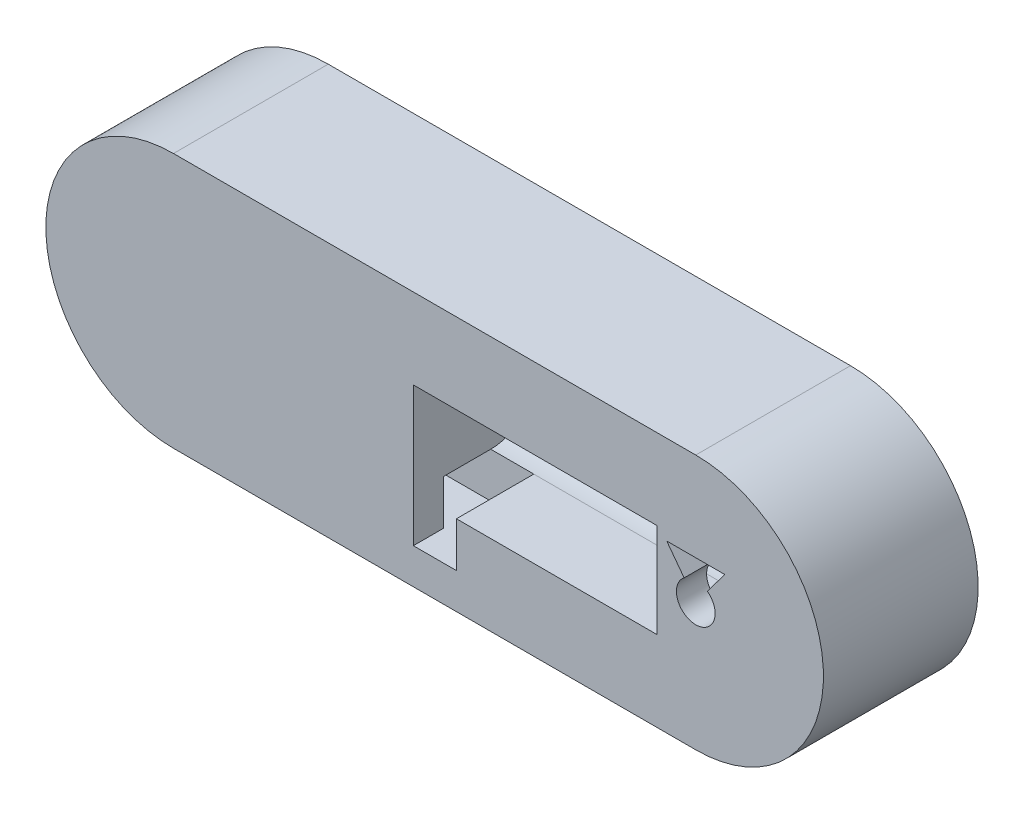
SolidWorks part; units mm, degrees
note: The reader was unsure of these and kept them because the rebuilt part matched: shared geometry of "Croquis1<4>".
ref_plane "Alzado" through (0, 0, 0) normal (0, 0, 1) x (1, 0, 0)
ref_plane "Planta" through (0, 0, 0) normal (0, 1, 0) x (1, 0, 0)
ref_plane "Vista lateral" through (0, 0, 0) normal (1, 0, 0) x (0, 0, -1)
sketch "Croquis1" plane through (0, 0, 0) normal (0, 0, 1) x (1, 0, 0)
  line L0 (-58.0271, -33) -> (76.9729, -33)
  line L1 (-58.0271, 33) -> (76.9729, 33)
  line L2 (-54.2341, 3.2577) -> (-54.2341, -3.2577)
  line L3 (69.4729, 10) -> (73.9729, 4)
  line L4 (73.9729, 4) -> (79.9729, 4)
  line L5 (79.9729, 4) -> (84.4729, 10)
  line L6 (84.4729, 10) -> (69.4729, 10)
  circle A0 centre (-58.0271, 0) radius 33
  circle A1 centre (76.9729, 0) radius 33
  circle A2 centre (-58.0271, 0) radius 5
  circle A3 centre (76.9729, 0) radius 5
  dimension "D2" = 10
  dimension "D3" = 10
  dimension "D4" = 66
  dimension "D1" = 135
  dimension "D5" = 15
  dimension "D6" = 6
extrude "Saliente-Extruir1" add sketch "Croquis1" along normal blind 40 contours A0 L0 A2 | A1 L1 A0 L0 | L1 A1 A3 | A2 | L2 A2
extrude "Cortar-Extruir2" cut sketch "Croquis1<4>" along normal blind 10 contours L2 A2
sketch "Croquis1<4>" plane through (0, 0, 0) normal (0, 0, 1) x (1, 0, 0) same geometry as "Croquis1"
sketch "Croquis5" plane through (0, 0, 40) normal (0, 0, 1) x (1, 0, 0)
  line L0 (15.1104, -23.8) -> (15.1104, -12.2)
  line L1 (15.1104, -12.2) -> (66.9729, -12.2)
  line L9 (3.9729, 12.2) -> (3.9729, -23.8)
  line L10 (66.9729, -12.2) -> (66.9729, 12.2)
  line L13 (3.9729, -23.8) -> (15.1104, -23.8)
  line L14 (66.9729, 12.2) -> (3.9729, 12.2)
  arc A0 (76.9729, -33) -> (76.9729, 33) centre (76.9729, 0) ccw construction
  arc A1 (76.9729, -33) -> (76.9729, 33) centre (76.9729, 0) ccw
  circle A2 centre (76.9729, 0) radius 5 construction
  circle A3 centre (76.9729, 0) radius 5
  point P2 (66.9729, 0)
  dimension "D2" = 10
  dimension "D3" = 63
  dimension "D4" = 24.4
  dimension "D1" = 11.6
extrude "Cortar-Extruir4" cut sketch "Croquis5" against normal blind 20 contours L10 L14 L9 L13 L0 L1
ref_plane "Plano2" through (3.9729, 0, 0) normal (1, 0, 0) x (0, 0, -1)
sketch "Croquis6" plane through (3.9729, 0, 0) normal (1, 0, 0) x (0, 0, -1)
  line L0 (-20, 12.2) -> (-40, 12.2)
  line L1 (-20, -12.2) -> (-40, -12.2)
  line L2 (-20, -23.8) -> (-20, -12.2)
  line L4 (-40, 12.2) -> (-40, -23.8)
  line L5 (-40, -23.8) -> (-20, -23.8)
  line L6 (-20, -23.8) -> (-20, 12.2)
  line L7 (-20, 12.2) -> (-40, 12.2)
  line L8 (-40, 12.2) -> (-40, -23.8)
  line L9 (-40, -23.8) -> (-20, -23.8)
  line L11 (-20, 12.2) -> (-40, 12.2)
  line L16 (0, -33) -> (0, 33)
  line L17 (0, 33) -> (-40, 33)
  line L18 (-40, 33) -> (-40, -33)
  line L19 (-40, -33) -> (0, -33)
  line L20 (0, -33) -> (0, 33)
  line L21 (0, 33) -> (-40, 33)
  line L22 (-40, 33) -> (-40, -33)
  line L23 (-40, -33) -> (0, -33)
  circle A0 centre (-20, 0) radius 12.2
  dimension "D2" = 24.4
  dimension "D3" = 0
  dimension "D1" = 0
extrude "Cortar-Extruir6" cut sketch "Croquis6" along direction (1, 0, 0) on the side of the normal up to surface (63 mm away) contours A0 | A0 L0 L8 L1
sketch "Croquis7" plane through (66.9729, 0, 0) normal (-1, 0, 0) x (0, 0, 1)
  line L1 (40, -12.2) -> (40.0638, -12.2)
  line L3 (20, -12.2) -> (7.8, -12.2)
  line L4 (20, -12.2) -> (20, 12.2) construction
  line L5 (20, 12.2) -> (7.8, 12.2)
  line L9 (40, 12.2) -> (40.0638, 12.2)
  line L11 (7.8, -12.2) -> (7.8, 12.2)
  line L12 (40, -12.2) -> (40, 12.2)
  line L13 (40, 12.2) -> (20, 12.2)
  line L16 (20, -12.2) -> (40, -12.2)
  line L17 (40, -12.2) -> (40, 12.2)
  line L22 (40, 12.2) -> (20, 12.2)
  line L26 (7.8, -12.2) -> (32.2, -12.2)
  line L27 (7.8, -12.2) -> (7.8, 12.2)
  line L28 (7.8, 12.2) -> (32.2, 12.2)
  line L29 (32.2, -12.2) -> (32.2, 12.2)
  line L31 (20, -12.2) -> (40, -12.2)
  circle A0 centre (20, 0) radius 12.2 construction
  arc A1 (20, 12.2) -> (20, -12.2) centre (20, 0) ccw
  arc A7 (20, 12.2) -> (20, -12.2) centre (20, 0) ccw
  dimension "D1" = 0
extrude "Cortar-Extruir9" cut sketch "Croquis7" against normal blind 30
sketch "Croquis8" plane through (3.9729, 0, 0) normal (1, 0, 0) x (0, 0, -1)
  line L0 (-32.2, -12.2) -> (-32.2, -23.8)
  line L5 (-40, -12.2) -> (-32.2, -12.2)
  line L6 (-40, 12.2) -> (-40, -12.2)
  line L8 (-40, -12.2) -> (-40, -23.8)
  line L9 (-20, -12.2) -> (-40, -12.2)
  line L10 (-20, -23.8) -> (-20, -12.2)
  line L11 (-40, -23.8) -> (-20, -23.8)
  line L12 (-40, -12.2) -> (-40, -23.8)
  line L13 (-20, -12.2) -> (-32.2, -12.2)
  line L14 (-20, -23.8) -> (-20, -12.2)
  line L15 (-40, -23.8) -> (-20, -23.8)
  line L18 (-40, 12.2) -> (-40, -12.2)
  line L20 (-32.2, -12.2) -> (-32.2, 12.2)
  line L21 (-32.2, 12.2) -> (-40, 12.2)
  line L23 (-32.2, 12.2) -> (-40, 12.2)
  line M10 (-40, -23.8) -> (-20, -23.8)
  line M11 (-20, -23.8) -> (-20, -12.2)
  dimension "D1" = 0
  dimension "D2" = 0
extrude "Cortar-Extruir10" cut sketch "Croquis8" against normal blind 50 contours L13 L0 M11 M10
sketch "Croquis9" plane through (0, 0, 0) normal (0, 0, -1) x (-1, 0, 0)
  line L0 (34.4271, -23.8) -> (34.4271, -12.2)
  line L7 (46.0271, -12.2) -> (-3.9729, -12.2)
  line L8 (-3.9729, -12.2) -> (-3.9729, -23.8)
  line L9 (-3.9729, -23.8) -> (46.0271, -23.8)
  line L10 (46.0271, -23.8) -> (46.0271, -12.2)
  line L13 (34.4271, -23.8) -> (46.0271, -23.8)
  line L14 (46.0271, -23.8) -> (46.0271, -12.2)
  line L16 (46.0271, -12.2) -> (-3.9729, -12.2)
  dimension "D2" = 0
extrude "Cortar-Extruir11" cut sketch "Croquis9" against normal up to next contours L14 L16 L0 L13
chamfer "Chaflán1" distance 10 angle 45 1 edges at (-46.0271, -18, 0)
